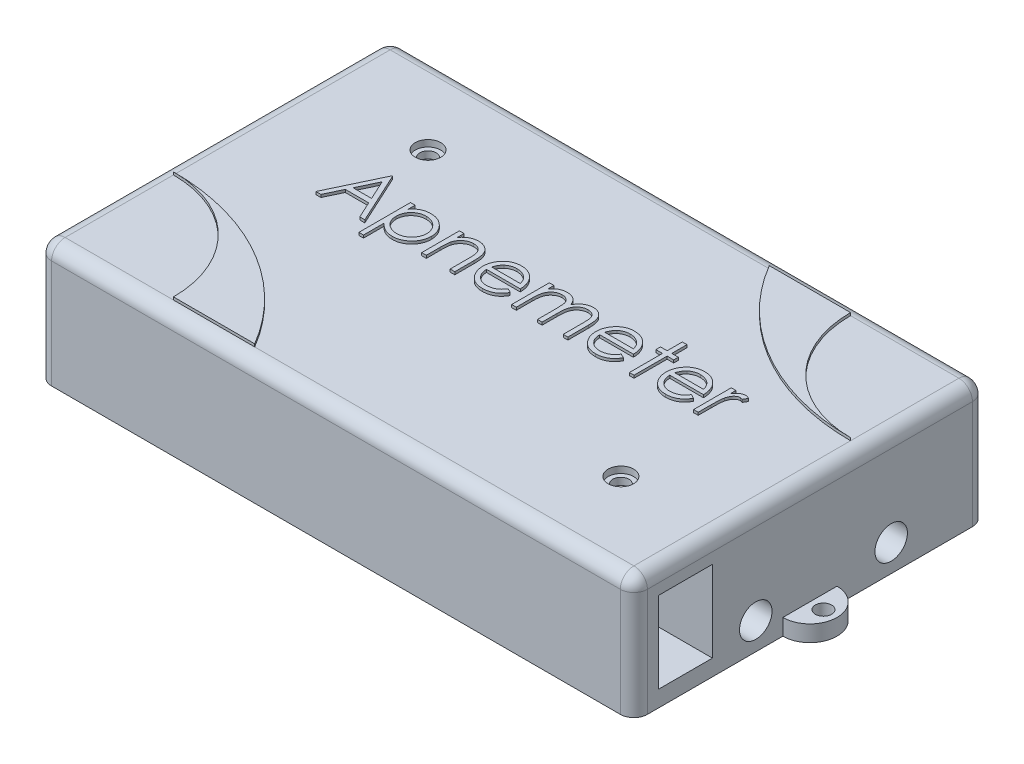
SolidWorks part; units mm, degrees
ref_plane "Front Plane" through (0, 0, 0) normal (0, 0, 1) x (1, 0, 0)
ref_plane "Top Plane" through (0, 0, 0) normal (0, 1, 0) x (1, 0, 0)
ref_plane "Right Plane" through (0, 0, 0) normal (1, 0, 0) x (0, 0, -1)
sketch "Sketch1" plane through (0, 0, 0) normal (0, 1, 0) x (1, 0, 0)
  line L1 (52.5, -30) -> (-52.5, -30)
  line L2 (52.5, -30) -> (52.5, 30)
  line L3 (52.5, 30) -> (-52.5, 30)
  line L4 (-52.5, -30) -> (-52.5, 30)
  line L5 (52.5, -30) -> (-52.5, 30) construction
  line L6 (52.5, 30) -> (-52.5, -30) construction
  point P0 (0, 0)
  dimension "D1" = 60
  dimension "D2" = 105
extrude "Boss-Extrude1" add sketch "Sketch1" along normal blind 20
shell "Shell1" thickness 2.5 removed face at (0, 0, 0) outward yes
sketch "Sketch2" plane through (0, 22.5, 0) normal (0, 1, 0) x (1, 0, 0)
  line L0 (55, 32.5) -> (-55, 32.5) construction
  line L1 (-55, 32.5) -> (-55, -32.5) construction
  line L2 (-55, -32.5) -> (55, -32.5) construction
  line L3 (55, -32.5) -> (55, 32.5) construction
  circle A3 centre (-33, 17.5) radius 1.5
  circle A4 centre (37, -16.9) radius 1.5
  dimension "D1" = 70
  dimension "D4" = 3
  dimension "D2" = 15
  dimension "D7" = 3
  dimension "D3" = 22
  dimension "D5" = 34.4
extrude "Cut-Extrude1" cut sketch "Sketch2" against normal blind 2.5
fillet "Fillet1" radius 2.5 4 edges at (55, 22.5, 0) (0, 22.5, -32.5) (-55, 22.5, 0) (0, 22.5, 32.5)
fillet "Fillet2" radius 2.5 8 edges at (54.2678, 21.7678, 31.7678) (-54.2678, 21.7678, -31.7678) (54.2678, 21.7678, -31.7678) (55, 10, 32.5) (-55, 10, -32.5) (55, 10, -32.5) (-54.2678, 21.7678, 31.7678) (-55, 10, 32.5)
sketch "Sketch3" plane through (0, 0, 0) normal (0, -1, 0) x (1, 0, 0)
  line L0 (-55, 0) -> (55, 0) construction
  line L1 (-55, -30) -> (-55, 30) construction
  line L2 (55, 30) -> (55, -30) construction
  line L3 (-55, -5) -> (-55, 5)
  line L4 (0, 0) -> (0, 30) construction
  line L5 (-52.5, 30) -> (52.5, 30) construction
  line L6 (0, 0) -> (0, -30) construction
  line L7 (52.5, -30) -> (-52.5, -30) construction
  arc A0 (-55, 5) -> (-55, -5) centre (-55, 0) ccw
  circle A1 centre (-57.5, 0) radius 1.5
  circle A2 centre (57.5, 0) radius 1.5
  arc A3 (55, 5) -> (55, -5) centre (55, 0) cw
  line M9 (-55, 30) -> (-55, -30)
  line M13 (55, -30) -> (55, 30)
  dimension "D2" = 3
  dimension "D1" = 10
  dimension "D3" = 2.5
extrude "Boss-Extrude2" add sketch "Sketch3" against normal blind 3 separate body contours A0 A1 M9 | A3 A2 M13 region at (-59.8882, 0, 0) region at (59.8882, 0, 0)
sketch "Sketch4" plane through (0, 22.5, 0) normal (0, 1, 0) x (1, 0, 0)
  circle A0 centre (-33, 17.5) radius 2.35
  circle A1 centre (37, -16.9) radius 2.35
  dimension "D1" = 4.7
  dimension "D2" = 4.7
extrude "Cut-Extrude2" cut sketch "Sketch4" against normal blind 1.2
sketch "Sketch10" plane through (-52.5, 0, 0) normal (1, 0, 0) x (0, 0, -1)
  line L1 (23, 19) -> (25, 19)
  line L2 (23, 19) -> (23, 0)
  line L3 (23, 0) -> (25, 0)
  line L4 (25, 19) -> (25, 0)
  line L5 (30, 0) -> (30, 20) construction
  line L10 (-4, 19) -> (-2, 19)
  line L11 (-2, 19) -> (-2, 0)
  line L12 (-4, 0) -> (-2, 0)
  line L13 (-4, 19) -> (-4, 0)
  dimension "D1" = 2
  dimension "D2" = 2
  dimension "D4" = 5
extrude "Boss-Extrude4" add sketch "Sketch10" along normal blind 17
sketch "Sketch11" plane through (0, 0, -25) normal (0, 0, -1) x (-1, 0, 0)
  line L0 (52.5, 0) -> (52.5, 20) construction
  line L1 (52.5, 17.5) -> (37, 17.5)
  line L2 (52.5, 17.5) -> (52.5, 1.5)
  line L3 (52.5, 1.5) -> (37, 1.5)
  line L4 (37, 17.5) -> (37, 1.5)
  line L6 (-52.5, 0) -> (52.5, 0) construction
  dimension "D1" = 16
  dimension "D2" = 15.5
  dimension "D3" = 1.5
extrude "Cut-Extrude4" cut sketch "Sketch11" against normal blind 5
sketch "Sketch14" plane through (0, 0, 4) normal (0, 0, 1) x (1, 0, 0)
  line L0 (-52.5, 20) -> (-52.5, 0) construction
  line L1 (-52.5, 17.5) -> (-44.5, 17.5)
  line L2 (-52.5, 17.5) -> (-52.5, 1.5)
  line L3 (-52.5, 1.5) -> (-44.5, 1.5)
  line L4 (-44.5, 17.5) -> (-44.5, 1.5)
  line L6 (52.5, 20) -> (-52.5, 20) construction
  dimension "D1" = 8
  dimension "D2" = 16
  dimension "D3" = 2.5
extrude "Cut-Extrude5" cut sketch "Sketch14" against normal blind 6
sketch "Sketch15" plane through (-52.5, 0, 0) normal (1, 0, 0) x (0, 0, -1)
  line L0 (-30, 0) -> (30, 0) construction
  line L1 (7, 19) -> (10, 19)
  line L2 (7, 19) -> (7, 0)
  line L3 (7, 0) -> (10, 0)
  line L4 (10, 19) -> (10, 0)
  line L5 (30, 0) -> (30, 20) construction
  dimension "D1" = 3
  dimension "D2" = 19
  dimension "D3" = 20
extrude "Boss-Extrude5" add sketch "Sketch15" along normal blind 10
sketch "Sketch17" plane through (0, 0, -7) normal (0, 0, 1) x (1, 0, 0)
  line L0 (-52.5, 20) -> (-52.5, 0) construction
  line L1 (-52.5, 17.5) -> (-44.5, 17.5)
  line L2 (-52.5, 17.5) -> (-52.5, 1.5)
  line L3 (-52.5, 1.5) -> (-44.5, 1.5)
  line L4 (-44.5, 17.5) -> (-44.5, 1.5)
  line L5 (52.5, 20) -> (-52.5, 20) construction
  dimension "D1" = 8
  dimension "D2" = 16
  dimension "D3" = 2.5
extrude "Cut-Extrude6" cut sketch "Sketch17" against normal blind 5
sketch "Sketch19" plane through (0, 0, 4) normal (0, 0, 1) x (1, 0, 0)
  line L0 (-52.5, 20) -> (-52.5, 0) construction
  line L1 (-42.5, 17.5) -> (-37.5, 17.5)
  line L2 (-42.5, 17.5) -> (-42.5, 1.5)
  line L3 (-42.5, 1.5) -> (-37.5, 1.5)
  line L4 (-37.5, 17.5) -> (-37.5, 1.5)
  line L5 (52.5, 20) -> (-52.5, 20) construction
  point P6 (-42.5, 9.5)
  dimension "D1" = 5
  dimension "D2" = 16
  dimension "D3" = 10
  dimension "D4" = 2.5
extrude "Cut-Extrude7" cut sketch "Sketch19" against normal blind 5
sketch "Sketch20" plane through (52.5, 0, 0) normal (-1, 0, 0) x (0, 0, 1)
  line L0 (30, 20) -> (-30, 20) construction
  line L1 (-30, 20) -> (-30, 0) construction
  circle A0 centre (-15, 5) radius 3.5
  circle A2 centre (10, 5) radius 3.5
  dimension "D1" = 7
  dimension "D3" = 15
  dimension "D2" = 15
  dimension "D4" = 2
extrude "Boss-Extrude7" add sketch "Sketch20" along normal blind 5
sketch "Sketch28" plane through (47.5, 0, 0) normal (-1, 0, 0) x (0, 0, 1)
  line L0 (30, 20) -> (-30, 20) construction
  line L1 (-30, 20) -> (-30, 0) construction
  circle A0 centre (-15, 5) radius 3
  circle A1 centre (10, 5) radius 3
  dimension "D1" = 6
  dimension "D2" = 15
  dimension "D3" = 15
  dimension "D4" = 2
extrude "Cut-Extrude12" cut sketch "Sketch28" against normal blind 10.5
sketch "Sketch23" plane through (-52.5, 0, 0) normal (1, 0, 0) x (0, 0, -1)
  line L0 (30, 20) -> (-30, 20) construction
  line L1 (-26.5, 17) -> (-25.5, 17)
  line L2 (-26.5, 17) -> (-26.5, 10)
  line L3 (-26.5, 10) -> (-25.5, 10)
  line L4 (-25.5, 17) -> (-25.5, 10)
  line L5 (-30, 20) -> (-30, 0) construction
  line L6 (-23.5, 17) -> (-23.5, 10)
  line L7 (-24.5, 17) -> (-24.5, 10)
  line L8 (-24.5, 17) -> (-23.5, 17)
  line L9 (-24.5, 10) -> (-23.5, 10)
  line L10 (-21.5, 17) -> (-21.5, 10)
  line L11 (-22.5, 17) -> (-22.5, 10)
  line L12 (-22.5, 17) -> (-21.5, 17)
  line L13 (-22.5, 10) -> (-21.5, 10)
  line L14 (-19.5, 17) -> (-19.5, 10)
  line L15 (-20.5, 17) -> (-20.5, 10)
  line L16 (-20.5, 17) -> (-19.5, 17)
  line L17 (-20.5, 10) -> (-19.5, 10)
  line L18 (-17.5, 17) -> (-17.5, 10)
  line L19 (-18.5, 17) -> (-18.5, 10)
  line L20 (-18.5, 17) -> (-17.5, 17)
  line L21 (-18.5, 10) -> (-17.5, 10)
  line L22 (-15.5, 17) -> (-15.5, 10)
  line L23 (-16.5, 17) -> (-16.5, 10)
  line L24 (-16.5, 17) -> (-15.5, 17)
  line L25 (-16.5, 10) -> (-15.5, 10)
  line L26 (-13.5, 17) -> (-13.5, 10)
  line L27 (-14.5, 17) -> (-14.5, 10)
  line L28 (-14.5, 17) -> (-13.5, 17)
  line L29 (-14.5, 10) -> (-13.5, 10)
  line L30 (-11.5, 17) -> (-11.5, 10)
  line L31 (-12.5, 17) -> (-12.5, 10)
  line L32 (-12.5, 17) -> (-11.5, 17)
  line L33 (-12.5, 10) -> (-11.5, 10)
  line L34 (-9.5, 17) -> (-9.5, 10)
  line L35 (-10.5, 17) -> (-10.5, 10)
  line L36 (-10.5, 17) -> (-9.5, 17)
  line L37 (-10.5, 10) -> (-9.5, 10)
  line L38 (-7.5, 17) -> (-7.5, 10)
  line L39 (-8.5, 17) -> (-8.5, 10)
  line L40 (-8.5, 17) -> (-7.5, 17)
  line L41 (-8.5, 10) -> (-7.5, 10)
  line L42 (-5.5, 17) -> (-5.5, 10)
  line L43 (-6.5, 17) -> (-6.5, 10)
  line L44 (-6.5, 17) -> (-5.5, 17)
  line L45 (-6.5, 10) -> (-5.5, 10)
  line L54 (0.5, 17) -> (0.5, 10)
  line L55 (-0.5, 17) -> (-0.5, 10)
  line L56 (-0.5, 17) -> (0.5, 17)
  line L57 (-0.5, 10) -> (0.5, 10)
  line L58 (2.5, 17) -> (2.5, 10)
  line L59 (1.5, 17) -> (1.5, 10)
  line L60 (1.5, 17) -> (2.5, 17)
  line L61 (1.5, 10) -> (2.5, 10)
  line L62 (4.5, 17) -> (4.5, 10)
  line L63 (3.5, 17) -> (3.5, 10)
  line L64 (3.5, 17) -> (4.5, 17)
  line L65 (3.5, 10) -> (4.5, 10)
  line L66 (6.5, 17) -> (6.5, 10)
  line L67 (5.5, 17) -> (5.5, 10)
  line L68 (5.5, 17) -> (6.5, 17)
  line L69 (5.5, 10) -> (6.5, 10)
  line L78 (12.5, 17) -> (12.5, 10)
  line L79 (11.5, 17) -> (11.5, 10)
  line L80 (11.5, 17) -> (12.5, 17)
  line L81 (11.5, 10) -> (12.5, 10)
  line L82 (14.5, 17) -> (14.5, 10)
  line L83 (13.5, 17) -> (13.5, 10)
  line L84 (13.5, 17) -> (14.5, 17)
  line L85 (13.5, 10) -> (14.5, 10)
  line L86 (16.5, 17) -> (16.5, 10)
  line L87 (15.5, 17) -> (15.5, 10)
  line L88 (15.5, 17) -> (16.5, 17)
  line L89 (15.5, 10) -> (16.5, 10)
  line L90 (18.5, 17) -> (18.5, 10)
  line L91 (17.5, 17) -> (17.5, 10)
  line L92 (17.5, 17) -> (18.5, 17)
  line L93 (17.5, 10) -> (18.5, 10)
  line L94 (20.5, 17) -> (20.5, 10)
  line L95 (19.5, 17) -> (19.5, 10)
  line L96 (19.5, 17) -> (20.5, 17)
  line L97 (19.5, 10) -> (20.5, 10)
  line L98 (22.5, 17) -> (22.5, 10)
  line L99 (21.5, 17) -> (21.5, 10)
  line L100 (21.5, 17) -> (22.5, 17)
  line L101 (21.5, 10) -> (22.5, 10)
  line L106 (26.5, 17) -> (26.5, 10)
  line L107 (25.5, 17) -> (25.5, 10)
  line L108 (25.5, 17) -> (26.5, 17)
  line L109 (25.5, 10) -> (26.5, 10)
  line L110 (-3.5, 17) -> (-3.5, 10) [skipped]
  line L111 (-4.5, 17) -> (-4.5, 10) [skipped]
  line L112 (-4.5, 17) -> (-3.5, 17) [skipped]
  line L113 (-4.5, 10) -> (-3.5, 10) [skipped]
  line L114 (-1.5, 17) -> (-1.5, 10) [skipped]
  line L115 (-2.5, 17) -> (-2.5, 10) [skipped]
  line L116 (-2.5, 17) -> (-1.5, 17) [skipped]
  line L117 (-2.5, 10) -> (-1.5, 10) [skipped]
  line L118 (8.5, 17) -> (8.5, 10) [skipped]
  line L119 (7.5, 17) -> (8.5, 17) [skipped]
  line L120 (10.5, 17) -> (10.5, 10) [skipped]
  line L121 (9.5, 17) -> (9.5, 10) [skipped]
  line L122 (9.5, 17) -> (10.5, 17) [skipped]
  line L123 (9.5, 10) -> (10.5, 10) [skipped]
  line L124 (7.5, 17) -> (7.5, 10) [skipped]
  line L125 (7.5, 10) -> (8.5, 10) [skipped]
  line L126 (24.5, 17) -> (24.5, 10) [skipped]
  line L127 (23.5, 17) -> (23.5, 10) [skipped]
  line L128 (23.5, 17) -> (24.5, 17) [skipped]
  line L129 (23.5, 10) -> (24.5, 10) [skipped]
  point P6 (-26, 17)
  dimension "D1" = 7
  dimension "D2" = 1
  dimension "D3" = 3
  dimension "D4" = 3.5
  dimension "D5" = 27
extrude "Cut-Extrude9" cut sketch "Sketch23" against normal blind 2.5
sketch "Sketch24" plane through (0, 22.5, 0) normal (0, 1, 0) x (1, 0, 0)
  line L0 (-52.5, 0) -> (52.5, 0) construction
  line L1 (-52.5, 30) -> (-52.5, -30) construction
  line L2 (52.5, -30) -> (52.5, 30) construction
  text T0 "Apnemeter" font "Century Gothic" height in points 36
extrude "Boss-Extrude8" add sketch "Sketch24" along normal blind 0.5
sketch "Sketch25" plane through (0, 22.5, 0) normal (0, 1, 0) x (1, 0, 0)
  line L0 (-52.5, 0) -> (52.5, 0) construction
  line L1 (-52.5, 30) -> (-52.5, -30) construction
  line L2 (52.5, -30) -> (52.5, 30) construction
  line L3 (32.5, 30) -> (52.5, 30) construction
  line L4 (52.5, 30) -> (52.5, 10)
  line L5 (52.5, 30) -> (-52.5, 30) construction
  line L6 (17.5, 30) -> (32.5, 30)
  line L7 (-32.5, -30) -> (-17.5, -30)
  line L8 (-52.5, -30) -> (52.5, -30) construction
  line L9 (-52.5, -30) -> (-52.5, -10) construction
  arc A0 (32.5, 30) -> (52.5, 10) centre (52.5, 30) ccw
  arc A1 (52.5, 10) -> (17.5, 30) centre (52.5, 50.625) cw
  arc A2 (-32.5, -30) -> (-52.5, -10) centre (-52.5, -30) ccw
  arc A3 (-52.5, -10) -> (-17.5, -30) centre (-52.5, -50.625) cw
  dimension "D1" = 40
  dimension "D3" = 40
  dimension "D2" = 15
  dimension "D4" = 15
extrude "Boss-Extrude9" add sketch "Sketch25" along normal blind 0.5 contours A1 A0 L6 | A3 A2 L7 region at (29.7974, 22.5, -22.3061) region at (-29.7974, 22.5, 22.3061)
sketch "Sketch26" plane through (55, 0, 0) normal (1, 0, 0) x (0, 0, -1)
  line L0 (30, 20) -> (-30, 20) construction
  line L1 (-28, 18) -> (-18, 18) construction
  line L2 (-28, 18) -> (-28, 3) construction
  line L3 (-28, 3) -> (-18, 3) construction
  line L4 (-18, 18) -> (-18, 3) construction
  line L5 (-30, 20) -> (-30, 0) construction
  line L6 (-29, 19) -> (-17, 19)
  line L7 (-17, 19) -> (-17, 2)
  line L8 (-29, 2) -> (-17, 2)
  line L9 (-29, 19) -> (-29, 2)
  dimension "D1" = 15
  dimension "D2" = 10
  dimension "D3" = 2
  dimension "D4" = 2
  dimension "D5" = 1
extrude "Boss-Extrude10" add sketch "Sketch26" against normal blind 9.5
sketch "Sketch27" plane through (55, 0, 0) normal (1, 0, 0) x (0, 0, -1)
  line L0 (-30, 20) -> (-30, 0) construction
  line L1 (-28, 18) -> (-18, 18)
  line L2 (-28, 18) -> (-28, 3)
  line L3 (-28, 3) -> (-18, 3)
  line L4 (-18, 18) -> (-18, 3)
  line L5 (30, 20) -> (-30, 20) construction
  dimension "D1" = 15
  dimension "D2" = 10
  dimension "D3" = 2
  dimension "D4" = 2
extrude "Cut-Extrude11" cut sketch "Sketch27" against normal blind 10.5 draft 5
